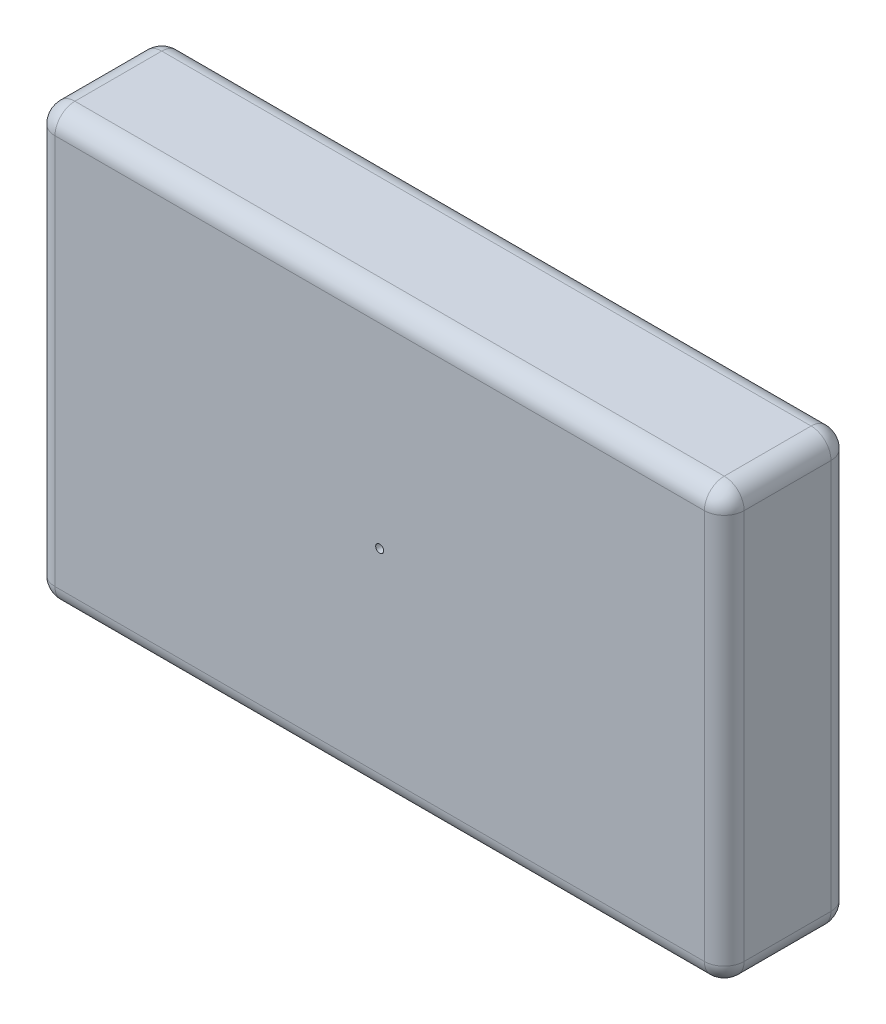
SolidWorks part; units mm, degrees
ref_plane "Alzado" through (0, 0, 0) normal (0, 0, 1) x (1, 0, 0)
ref_plane "Planta" through (0, 0, 0) normal (0, 1, 0) x (1, 0, 0)
ref_plane "Vista lateral" through (0, 0, 0) normal (1, 0, 0) x (0, 0, -1)
sketch "Croquis1" plane through (0, 0, 0) normal (0, 0, 1) x (1, 0, 0)
  line L1 (-86.5, 54) -> (86.5, 54)
  line L2 (-86.5, 54) -> (-86.5, -54)
  line L3 (-86.5, -54) -> (86.5, -54)
  line L4 (86.5, 54) -> (86.5, -54)
  line L5 (-86.5, 54) -> (86.5, -54) construction
  line L6 (-86.5, -54) -> (86.5, 54) construction
  point P0 (0, 0)
  dimension "D1" = 108
  dimension "D2" = 173
extrude "Saliente-Extruir1" add sketch "Croquis1" along normal blind 31.8
fillet "Redondeo1" radius 5 4 edges at (0, -54, 31.8) (-86.5, 0, 31.8) (0, 54, 31.8) (86.5, 0, 31.8)
fillet "Redondeo2" radius 5 4 edges at (0, 54, 0) (-86.5, 0, 0) (0, -54, 0) (86.5, 0, 0)
fillet "Redondeo3" radius 5 12 edges at (-85.0355, -52.5355, 30.3355) (-85.0355, -52.5355, 1.4645) (85.0355, -52.5355, 30.3355) (85.0355, -52.5355, 1.4645) (-85.0355, 52.5355, 30.3355) (-85.0355, 52.5355, 1.4645) (85.0355, 52.5355, 30.3355) (85.0355, 52.5355, 1.4645) (-86.5, -54, 15.9) (86.5, -54, 15.9) (-86.5, 54, 15.9) (86.5, 54, 15.9)
sketch "Croquis2" plane through (0, 0, 31.8) normal (0, 0, 1) x (1, 0, 0)
  circle A0 centre (0, 0) radius 1
extrude "Cortar-Extruir1" cut sketch "Croquis2" against normal blind 10
